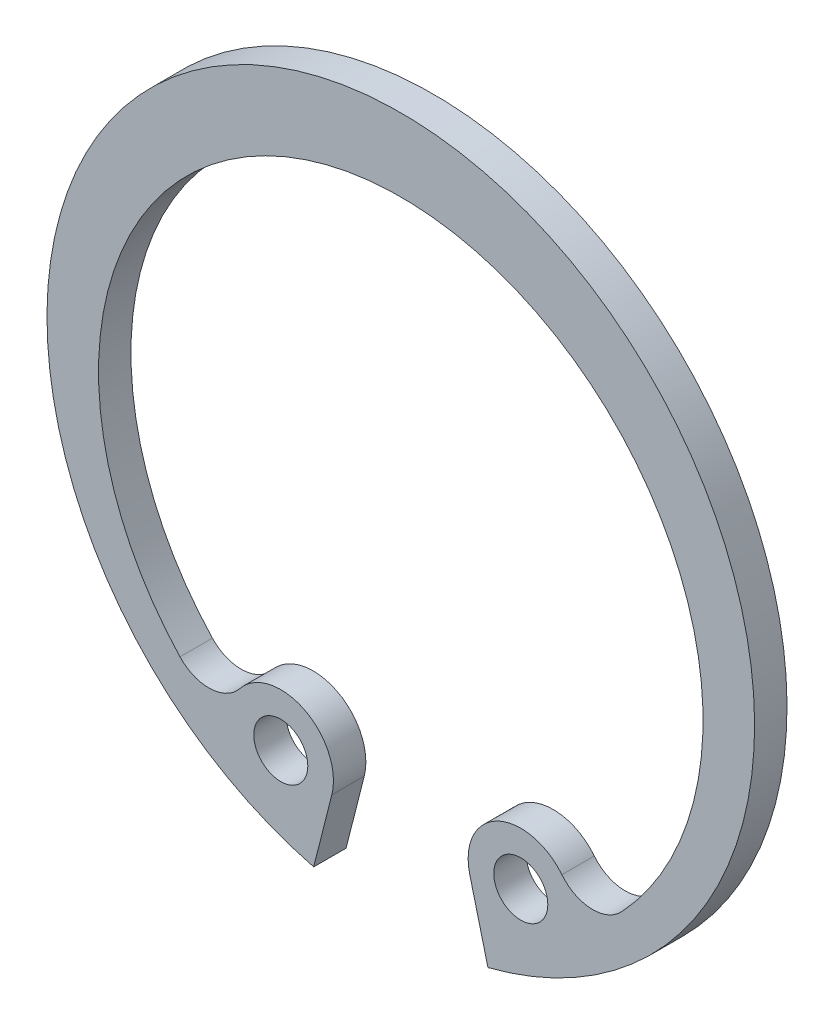
SolidWorks part; units mm, degrees
extrude "Body" add sketch "BodySke" against normal blind 1.2
sketch "BodySke" plane through (0, 0, 0) normal (0, 0, 1) x (1, 0, 0)
  line L0 (-1.5431, 0) -> (1.5431, 0) construction
  line L1 (0, 0) -> (0, 10.4) construction
  line L2 (3.2259, -12.6966) -> (2.5532, -10.0489)
  line L3 (-3.2259, -12.6966) -> (-2.5532, -10.0489)
  line L4 (0, 0) -> (9.0513, -9.4701) construction
  line L5 (0, 0) -> (-9.0513, -9.4701) construction
  line L6 (-4.1969, -8.5996) -> (-4.6894, -10.538) construction
  line L7 (4.2583, -8.8413) -> (4.628, -10.2962) construction
  arc A0 (-2.5532, -10.0489) -> (-5.9651, -8.3498) centre (-4.4431, -9.5688) ccw
  arc A1 (5.9651, -8.3498) -> (2.5532, -10.0489) centre (4.4431, -9.5688) ccw
  arc A2 (8.1185, -8.4942) -> (-8.1185, -8.4942) centre (0, -0.7913) ccw construction
  arc A3 (3.2259, -12.6966) -> (-3.2259, -12.6966) centre (0, 0) ccw
  circle A4 centre (4.4431, -9.5688) radius 1
  circle A5 centre (-4.4431, -9.5688) radius 1
  circle A6 centre (4.4431, -9.5688) radius 1.95 construction
  arc A7 (8.175, -8.4343) -> (-8.175, -8.4343) centre (0, -0.7913) ccw
  arc A8 (-4.4431, -9.5688) -> (4.4431, -9.5688) centre (0, 0) ccw construction
  arc A9 (-8.175, -8.4343) -> (-5.9651, -8.3498) centre (-7.1067, -7.4355) ccw
  arc A10 (5.9651, -8.3498) -> (8.175, -8.4343) centre (7.1067, -7.4355) ccw
  dimension "GrooveDia" = 26.2
  dimension "TipRad" = 1.95
  dimension "HoleDia" = 2
ref_plane "Plane1" through (0, 0, 0) normal (0, 0, 1) x (1, 0, 0)
ref_plane "Plane2" through (0, 0, 0) normal (0, 1, 0) x (1, 0, 0)
ref_plane "Plane3" through (0, 0, 0) normal (1, 0, 0) x (0, 0, -1)
sketch "Clipboard" plane through (0, 0, 0) normal (0, 0, 1) x (1, 0, 0)
  line L0 (0, 0) -> (2.7, 0)
  line L1 (0, 0) -> (0, 1.35)
  line L2 (0, 0) -> (0, -4.5)
  circle A0 centre (0, 0) radius 1
  circle A1 centre (0, 0) radius 12.5
  dimension "HoleDia" = 2
sketch "ModLugSke" plane through (0, 0, 0) normal (0, 0, 1) x (1, 0, 0)
  line L0 (3.2259, -12.6966) -> (2.1422, -8.4315)
  line L1 (-3.2259, -12.6966) -> (-2.1422, -8.4315)
  line L2 (7.0959, -4.8588) -> (10.8089, -7.4011) construction
  line L3 (-7.0959, -4.8588) -> (-10.8089, -7.4011) construction
  line L4 (-3.2259, -12.6966) -> (-2.5532, -10.0489) construction
  line L5 (2.5532, -10.0489) -> (3.2259, -12.6966) construction
  line L6 (0, 0) -> (0, -18.0732) construction
  line L7 (9.5814, -6.5606) -> (10.8089, -7.4011)
  line L8 (-10.8089, -7.4011) -> (-9.5814, -6.5606)
  arc A0 (3.2259, -12.6966) -> (10.8089, -7.4011) centre (0, 0) ccw
  arc A1 (-4.9183, -7.0548) -> (-2.2134, -8.3103) centre (0, 0) ccw
  arc A2 (3.2259, -12.6966) -> (-3.2259, -12.6966) centre (0, 0) ccw construction
  arc A3 (5.9651, -8.3498) -> (2.5532, -10.0489) centre (4.4431, -9.5688) ccw construction
  arc A4 (-4.9183, -7.0548) -> (-5.0436, -7.0637) centre (-4.9754, -7.1369) ccw
  arc A5 (-9.5814, -6.5606) -> (-5.0436, -7.0637) centre (-7.0959, -4.8588) ccw
  arc A6 (8.175, -8.4343) -> (-8.175, -8.4343) centre (0, -0.7913) ccw construction
  arc A7 (5.0436, -7.0637) -> (9.5814, -6.5606) centre (7.0959, -4.8588) ccw
  arc A8 (2.2134, -8.3103) -> (4.9183, -7.0548) centre (0, 0) ccw
  arc A9 (-10.8089, -7.4011) -> (-3.2259, -12.6966) centre (0, 0) ccw
  circle A10 centre (-4.4431, -9.5688) radius 1
  circle A11 centre (-4.4431, -9.5688) radius 1 construction
  circle A12 centre (4.4431, -9.5688) radius 1
  circle A13 centre (4.4431, -9.5688) radius 1 construction
  arc A14 (-2.2134, -8.3103) -> (-2.1422, -8.4315) centre (-2.2392, -8.4069) cw
  arc A15 (2.2134, -8.3103) -> (2.1422, -8.4315) centre (2.2392, -8.4069) ccw
  arc A16 (4.9183, -7.0548) -> (5.0436, -7.0637) centre (4.9754, -7.1369) cw
  point P43 (2.1178, -8.3352)
  dimension "D1" = 0.1
extrude "ModLug" [suppressed] add sketch "ModLugSke" against normal through all
sketch "UnlSke" [suppressed] plane through (0, 0, 0) normal (0, 0, 1) x (1, 0, 0)
  line L0 (2.1178, -8.3352) -> (3.2259, -12.6966)
  line L1 (-2.1178, -8.3352) -> (-3.2259, -12.6966)
  line L2 (-3.2259, -12.6966) -> (-2.1422, -8.4315) construction
  line L3 (2.1422, -8.4315) -> (3.2259, -12.6966) construction
  arc A0 (2.1178, -8.3352) -> (-2.1178, -8.3352) centre (0, 0) ccw
  arc A1 (3.2259, -12.6966) -> (-3.2259, -12.6966) centre (0, 0) ccw
  arc A2 (3.2259, -12.6966) -> (-3.2259, -12.6966) centre (0, 0) ccw construction
  circle A4 centre (-4.4431, -9.5688) radius 1
  circle A5 centre (4.4431, -9.5688) radius 1
  circle A6 centre (4.4431, -9.5688) radius 1 construction
  circle A7 centre (-4.4431, -9.5688) radius 1 construction
  arc A8 (2.2134, -8.3103) -> (4.9183, -7.0548) centre (0, 0) ccw construction
extrude "Unlug" [suppressed] add sketch "UnlSke" against normal through all
equation "' \"BoreDia@Clipboard\" = 8"
equation "' \"Thickness@Body\" = 0.8"
equation "' \"GrooveDia@BodySke\" = 8.4"
equation "' \"LugSection@Clipboard\" = 2.4"
equation "' \"LargeSection@Clipboard\" = 1.1"
equation "' \"HoleDia@Clipboard\" = 1"
equation "' \"BoreDia@Clipboard\" = 25"
equation "' \"Thickness@Body\" = 1.2"
equation "' \"GrooveDia@BodySke\" = 26.2"
equation "' \"LugSection@Clipboard\" = 4.5"
equation "' \"LargeSection@Clipboard\" = 2.7"
equation "' \"HoleDia@Clipboard\" = 2"
equation "\"SmallSection@Clipboard\" = \"LargeSection@Clipboard\" * 0.5"
equation "\"TipRad@BodySke\" = (\"LugSection@Clipboard\" - (\"GrooveDia@BodySke\" / 2  -  \"BoreDia@Clipboard\" / 2 ) ) / 2"
equation "\"HoleOffsetRad@BodySke\" = (\"GrooveDia@BodySke\" / 2) - \"LugSection@Clipboard\"  + \"TipRad@BodySke\""
equation "\"LargeRad@BodySke\" =  \"GrooveDia@BodySke\" / 2 -  \"LargeSection@Clipboard\""
equation "\"SmallRad@BodySke\" =  \"GrooveDia@BodySke\" / 2 -  \"SmallSection@Clipboard\""
equation "\"HoleDia@BodySke\" =  \"HoleDia@Clipboard\""
equation "\"FilletRad@BodySke\" = \"TipRad@BodySke\" * 0.75"
equation "\"GapAngle@BodySke\" = 360 - 0.965 * 360 * ( \"BoreDia@Clipboard\" /  \"GrooveDia@BodySke\")"
equation "\"LugAng@ModLugSke\" = \"GapAngle@BodySke\"  + 2 * 360 * (\"LugSection@Clipboard\" / (\"BoreDia@Clipboard\" * 3.1416))"
